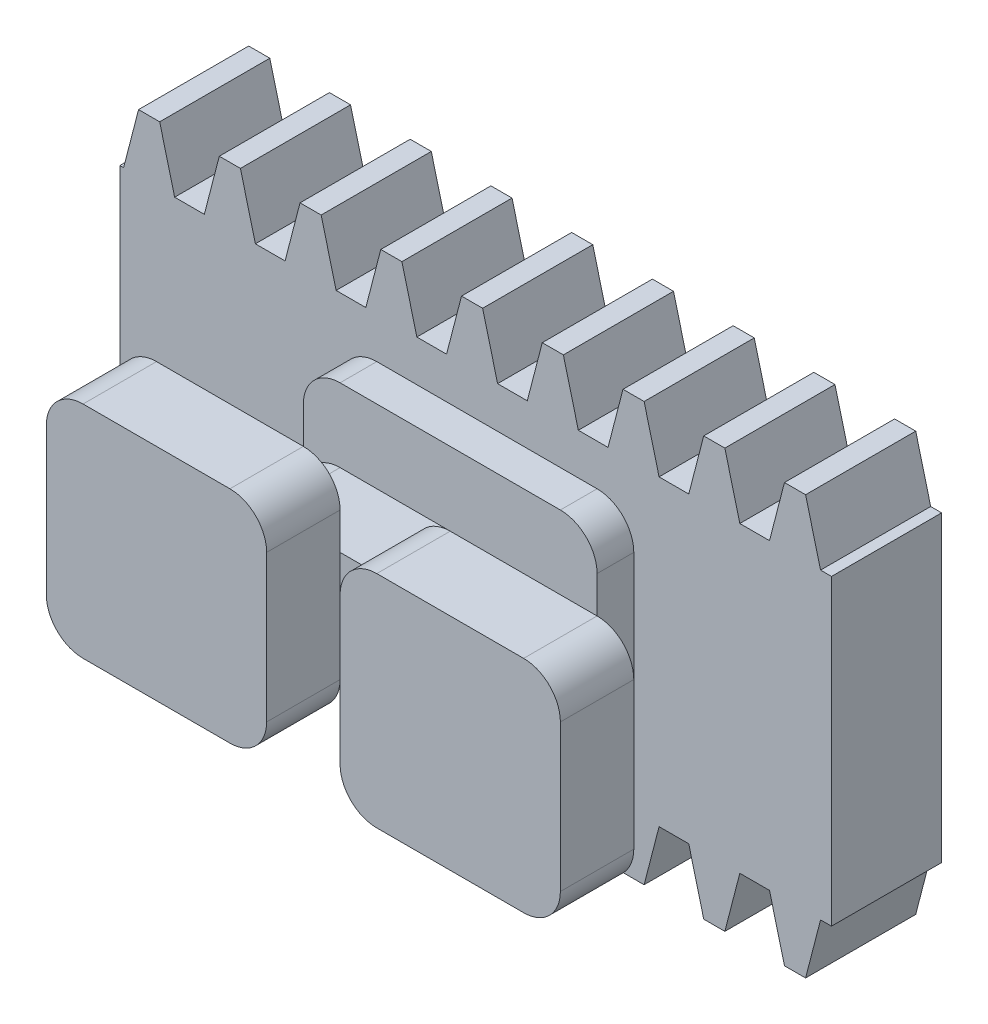
SolidWorks part; units mm, degrees
extrude "Blank" add sketch "BlankSke" against normal blind 3
sketch "BlankSke" plane through (0, 0, 0) normal (0, 0, 1) x (1, 0, 0)
  line L1 (0, 0) -> (25, 0)
  line L2 (0, 0) -> (0, 5.7)
  line L3 (0, 5.7) -> (25, 5.7)
  line L4 (25, 0) -> (25, 5.7)
  dimension "Length" = 25
ref_plane "Plane1" through (0, 0, 0) normal (0, 0, 1) x (1, 0, 0)
ref_plane "Plane2" through (0, 0, 0) normal (0, 1, 0) x (1, 0, 0)
ref_plane "Plane3" through (0, 0, 0) normal (1, 0, 0) x (0, 0, -1)
other "Configuration Table"
sketch "HoldingSke" plane through (0, 0, 0) normal (0, 1, 0) x (1, 0, 0)
  line L0 (0, 0) -> (0.1988, 1.4147)
  line L1 (-15, 0) -> (100, 0) construction
  line L2 (0, 0) -> (-2.1039, 2.3779)
  line L3 (0, 0) -> (-11.863, 4.5341)
  line L4 (0, 0) -> (8.4147, 1.9427)
  line L5 (0, 0) -> (-23.7986, -8.8762)
  line L6 (0, 0) -> (-10.5278, -7.1032)
  line L9 (-67.7845, 28.3722) -> (-43.5808, 34.6317)
  line L10 (-76.2, 3.0779) -> (-71.2, 3.0779)
  line L11 (0, 0) -> (-3, 0)
  line L12 (-76.2, 101.6) -> (-76.173, 101.6)
  line L13 (24.9733, 27.94) -> (52.9518, 28.4284)
  line L14 (24.9733, 27.94) -> (24.9743, 27.94)
  line L15 (24.9733, 27.94) -> (100.4006, 29.5858)
  circle A0 centre (0, 0) radius 19.05
  circle A1 centre (0, 0) radius 2.5
  circle A2 centre (0, 0) radius 12.7
  dimension "Num_teeth" = 13
  dimension "Width" = 3
  dimension "Length" = 25
  dimension "Pitch_height" = 5
sketch "TooCutSkeIll" plane through (0, 0, 0) normal (0, 0, 1) x (1, 0, 0)
  line L0 (-0.8064, 5.679) -> (-0.4386, 4.2569)
  line L1 (-0.2682, 4.125) -> (0.2682, 4.125)
  line L2 (0.4386, 4.2569) -> (0.8064, 5.679)
  line L3 (25, 5.7) -> (0, 5.7) construction
  line L4 (0, 0) -> (0, 64.897) construction
  line L5 (-13.208, 5) -> (12.954, 5) construction
  line L6 (0, 0) -> (25, 0) construction
  line L7 (0.6308, 5) -> (0.6308, 48.7463) construction
  line L8 (-0.6308, 5) -> (-0.6308, 48.7463) construction
  line L9 (0.8335, 5.7) -> (0.8335, 5.7254)
  line L10 (-0.8335, 5.7) -> (-0.8335, 5.7254)
  line L11 (-0.8335, 5.7254) -> (0.8335, 5.7254)
  arc A0 (0.2682, 4.125) -> (0.4386, 4.2569) centre (0.2682, 4.301) ccw
  arc A1 (-0.4386, 4.2569) -> (-0.2682, 4.125) centre (-0.2682, 4.301) ccw
  arc A2 (0.8335, 5.7) -> (0.8064, 5.679) centre (0.8335, 5.672) ccw
  arc A3 (-0.8064, 5.679) -> (-0.8335, 5.7) centre (-0.8335, 5.672) ccw
  dimension "Addendum_plus" = 0.7254
  dimension "Pitch_height" = 5
  dimension "Pressure_angle" = 14.5
  dimension "Gap_width" = 1.2616
  dimension "Dedendum" = 0.875
extrude "ToothCutIll" [suppressed] cut sketch "TooCutSkeIll" against normal through all
sketch "TooCutSkeSim" plane through (0, 0, 0) normal (0, 0, 1) x (1, 0, 0)
  line L0 (0.4045, 4.125) -> (-0.4045, 4.125)
  line L1 (0.8184, 5.7254) -> (0.4045, 4.125)
  line L2 (0, 17.4625) -> (0, 53.467) construction
  line L3 (0.8184, 5.7254) -> (-0.8184, 5.7254)
  line L6 (-0.8184, 5.7254) -> (-0.4045, 4.125)
  line L9 (-0.6308, 5) -> (0.6308, 5) construction
  line L10 (0, 0) -> (25, 0) construction
  line L11 (0.6308, 5) -> (0.6308, 53.467) construction
  line L12 (-0.6308, 5) -> (-0.6308, 53.467) construction
  dimension "Addendum_plus" = 0.7254
  dimension "Pitch_height" = 5
  dimension "Pressure_angle" = 14.5
  dimension "Gap_width" = 1.2616
  dimension "Dedendum" = 0.875
extrude "ToothCutSim" cut sketch "TooCutSkeSim" against normal through all
pattern_linear "TeethCuts" count 13 spacing 2.1991 along (1, 0, 0) of "ToothCutIll", "ToothCutSim"
mirror "镜向1" [suppressed]
mirror "镜向2" about plane through (0, 0, -3) normal (0, -1, 0) of "Blank", "ToothCutSim", "TeethCuts"
sketch "草图1" plane through (0, 0, 0) normal (-1, 0, 0) x (0, 0, 1)
  line L1 (0, 4.125) -> (0, -4.125) construction
  line L4 (-3, 0) -> (0, 0) construction
  line L5 (-3, 4.125) -> (-3, -4.125) construction
  line L7 (0, -3) -> (0, 3)
  line L8 (0, 3) -> (-2, 3.5)
  line L9 (-2, 3.5) -> (-2, -3.5)
  line L10 (0, -3) -> (-2, -3.5)
  point P11 (-2.5, 0)
  point P12 (-2, 0)
  dimension "D1" = 3
  dimension "D2" = 3.5
  dimension "D3" = 2
sketch "草图2" plane through (0, 0, -3) normal (0, 0, -1) x (-1, 0, 0)
  line L0 (0, 0) -> (-25, 0) construction
  line L1 (0, 4.125) -> (0, -4.125) construction
  line L2 (-25, -5.692) -> (-25, 5.692) construction
  circle A0 centre (-12.5, 0) radius 1.5
  dimension "D1" = 3
extrude "凸台-拉伸1" add sketch "草图2" along normal blind 2.5
sketch "草图3" plane through (0, 0, -5.5) normal (0, 0, -1) x (-1, 0, 0)
  circle A0 centre (-12.5, 0) radius 0.5
  dimension "D1" = 1
extrude "切除-拉伸3" cut sketch "草图3" against normal through all
sketch "草图4" plane through (0, 0, -3) normal (0, 0, -1) x (-1, 0, 0)
  line L0 (-12.5, 0) -> (-21.8848, 0) construction
  line L1 (-12.5, 0) -> (-2.5, 0) construction
  line L2 (-21.8848, 2.1496) -> (-21.8848, -2.1496)
  line L3 (-22.3956, 4.125) -> (-22.803, 5.7) construction
  line L4 (-2.5, 4.125) -> (-2.5, -4.125)
  line L6 (-1.7946, -4.125) -> (-2.6036, -4.125) construction
  line L7 (-22.3956, -4.125) -> (-22.803, -5.7) construction
  line L9 (-1.7946, 4.125) -> (-2.6036, 4.125) construction
  line L10 (-21.8848, 2.1496) -> (-21.8848, 5.9598)
  line L11 (-21.8848, 5.9598) -> (-25.6774, 5.9598)
  line L12 (-25.6774, 5.9598) -> (-25.6774, -6.5792)
  line L13 (-25.6774, -6.5792) -> (-21.8848, -6.5792)
  line L14 (-21.8848, -6.5792) -> (-21.8848, -2.1496)
  line L15 (-2.5, 4.125) -> (-2.5, 6.4022)
  line L16 (-2.5, 6.4022) -> (0, 6.4022)
  line L17 (0, 6.4022) -> (0, -6.0736)
  line L18 (0, -6.0736) -> (-2.5, -6.0736)
  line L19 (-2.5, -6.0736) -> (-2.5, -4.125)
  dimension "D2" = 10
extrude "切除-拉伸4" cut sketch "草图4" against normal blind 10
sketch "草图5" plane through (0, 0, 0) normal (0, 0, 1) x (1, 0, 0)
  line L0 (2.5, 2) -> (21.8848, 2)
  line L1 (2.5, 4.125) -> (2.5, -4.125) construction
  line L2 (21.8848, -4.125) -> (21.8848, 4.125) construction
  line L3 (21.8848, 2) -> (21.8848, -2)
  line L4 (21.8848, -2) -> (2.5, -2)
  line L5 (2.5, -2) -> (2.5, 2)
  point P8 (2.5, 0)
  point P9 (21.8848, 0)
  dimension "D1" = 4
sketch "草图6" plane through (0, 0, 0) normal (0, 0, 1) x (1, 0, 0)
  line L0 (1.1742, 0) -> (24.2349, 0) construction
  line L1 (8.5, 1) -> (8.5, -1)
  line L2 (8.5, -1) -> (16.5, -1)
  line L3 (16.5, -1) -> (16.5, 1)
  line L4 (16.5, 1) -> (8.5, 1)
  point P2 (16.5, 0)
  point P4 (12.5, 0)
  point P5 (8.5, 0)
  dimension "D1" = 2
  dimension "D2" = 8
  dimension "D3" = 4
extrude "凸台-拉伸3" add sketch "草图6" along normal blind 3
sketch "草图7" plane through (0, 0, 3) normal (0, 0, 1) x (1, 0, 0)
  line L0 (5.5, 3) -> (11.5, 3)
  line L1 (19.5, 3) -> (19.5, -3)
  line L2 (19.5, -3) -> (13.5, -3)
  line L3 (5.5, -3) -> (5.5, 3)
  line L5 (16.5, 1) -> (8.5, 1) construction
  line L6 (8.5, -1) -> (16.5, -1) construction
  line L7 (8.5, 1) -> (8.5, -1) construction
  line L8 (16.5, -1) -> (16.5, 1) construction
  line L9 (11.5, 3) -> (11.5, -3)
  line L10 (13.5, 3) -> (13.5, -3)
  line L11 (13.5, 3) -> (19.5, 3)
  line L12 (11.5, -3) -> (5.5, -3)
  dimension "D1" = 2
  dimension "D2" = 2
  dimension "D3" = 3
  dimension "D4" = 3
  dimension "D5" = 6
  dimension "D6" = 6
extrude "凸台-拉伸4" add sketch "草图7" along normal blind 2
fillet "圆角1" radius 1 4 edges at (16.5, -1, 1.5) (8.5, -1, 1.5) (16.5, 1, 1.5) (8.5, 1, 1.5)
fillet "圆角2" radius 1 8 edges at (5.5, -3, 4) (5.5, 3, 4) (11.5, 3, 4) (11.5, -3, 4) (13.5, -3, 4) (13.5, 3, 4) (19.5, 3, 4) (19.5, -3, 4)
sketch "草图8" plane through (0, 0, 0) normal (0, 0, 1) x (1, 0, 0)
  line L15 (8.5, 3) -> (8.5, -3)
  line L16 (10.5, 3) -> (6.5, 3) construction
  line L17 (6.5, -3) -> (10.5, -3) construction
  line L18 (8.5, -3) -> (16.5, -3)
  line L19 (14.5, -3) -> (18.5, -3) construction
  line L20 (16.5, -3) -> (16.5, 3)
  line L21 (16.5, 3) -> (8.5, 3)
  line L22 (11.5, -2) -> (11.5, 2) construction
  dimension "D1" = 3
  dimension "D2" = 8
extrude "凸台-拉伸5" add sketch "草图8" along normal blind 1
fillet "圆角5" radius 1 4 edges at (16.5, -3, 0.5) (8.5, -3, 0.5) (8.5, 3, 0.5) (16.5, 3, 0.5)
equation "' \"Module@HoldingSke\" = 6.35"
equation "' \"Num_teeth@HoldingSke\" = 12"
equation "' \"Ap@HoldingSke\" =  20"
equation "' \"Ap@HoldingSke\" = 20"
equation "' \"Width@HoldingSke\" = 0.25 * 25.4"
equation "' \"Show_teeth@HoldingSke\" = 500"
equation "' \"Backlash@HoldingSke\" = 0.009 * 25.4"
equation "' \"Addendum_fac@HoldingSke\" = 1.0"
equation "' \"Dedendum_fac@HoldingSke\" = 1.25"
equation "' \"Dedendum_add@HoldingSke\" = 0.00005 * 25.4"
equation "' \"Clearance_fac@HoldingSke\" = 0.25"
equation "' \"Pitch_height@HoldingSke\" = 1 * 25.4"
equation "' \"Length@HoldingSke\" = 4.71 * 25.4"
equation "\"Pitch@HoldingSke\" = 1 / \"Module@HoldingSke\""
equation "\"MPH@HoldingSke\" = \"Dedendum_fac@HoldingSke\" / \"Pitch@HoldingSke\" + 2 * \"Dedendum_add@HoldingSke\" + 0.002 * 25.4"
equation "\"MPH@HoldingSke\" = ((sgn( \"MPH@HoldingSke\" - \"Pitch_height@HoldingSke\")+1)*( \"MPH@HoldingSke\" - \"Pitch_height@HoldingSke\"))/2 + \"Pitch_height@HoldingSke\""
equation "\"Blank_height@BlankSke\" = \"Pitch_height@HoldingSke\" + \"Addendum_fac@HoldingSke\"  / \"Pitch@HoldingSke\" "
equation "\"Length@BlankSke\" =  \"Length@HoldingSke\""
equation "\"Face_width@Blank\" = \"Width@HoldingSke\""
equation "\"Pressure_angle@TooCutSkeIll\" = \"Ap@HoldingSke\""
equation "\"Addendum_plus@TooCutSkeIll\" =  \"Addendum_fac@HoldingSke\"  / \"Pitch@HoldingSke\" + 0.001 *25.4"
equation "\"Dedendum@TooCutSkeIll\" = \"Dedendum_fac@HoldingSke\"  / \"Pitch@HoldingSke\""
equation "\"Pitch_height@TooCutSkeIll\" =  \"MPH@HoldingSke\""
equation "\"Gap_width@TooCutSkeIll\" = 3.14159265 / 2 / \"Pitch@HoldingSke\" + 6 * \"Backlash@HoldingSke\""
equation "\"Pressure_angle@TooCutSkeSim\" = \"Ap@HoldingSke\""
equation "\"Addendum_plus@TooCutSkeSim\" =  \"Addendum_fac@HoldingSke\"  / \"Pitch@HoldingSke\" + 0.001 * 25.4"
equation "\"Dedendum@TooCutSkeSim\" = \"Dedendum_fac@HoldingSke\"  / \"Pitch@HoldingSke\""
equation "\"Pitch_height@TooCutSkeSim\" =  \"MPH@HoldingSke\""
equation "\"Gap_width@TooCutSkeSim\" = 3.14159265 / 2 / \"Pitch@HoldingSke\" + 6 * \"Backlash@HoldingSke\""
equation "\"Root_fillet@TooCutSkeIll\" = \"Clearance_fac@HoldingSke\" / \"Pitch@HoldingSke\" + \"Dedendum_add@HoldingSke\""
equation "\"Break_rad@TooCutSkeIll\" = 0.02 / \"Pitch@HoldingSke\" * 2"
equation "\"Linear_pitch@TeethCuts\" = 3.14159265 / \"Pitch@HoldingSke\""
equation "\"Num_teeth@HoldingSke\" = int( ( \"Length@HoldingSke\" + 0 ) / (3.14159265 / \"Pitch@HoldingSke\")) + 0.9999  + 1"
equation " \"Num_teeth@TeethCuts\" = int( \"Show_teeth@HoldingSke\" ) + 1"
equation " \"Num_teeth@TeethCuts\" = ((sgn( \"Num_teeth@TeethCuts\" - \"Num_teeth@HoldingSke\" )-1)*( \"Num_teeth@TeethCuts\" - \"Num_teeth@HoldingSke\" ))/-2+ \"Num_teeth@HoldingSke\""
equation " \"Num_teeth@TeethCuts\" = ((sgn( \"Num_teeth@TeethCuts\" - 2.0)+1)*( \"Num_teeth@TeethCuts\" - 2.0))/2 +2.0"
